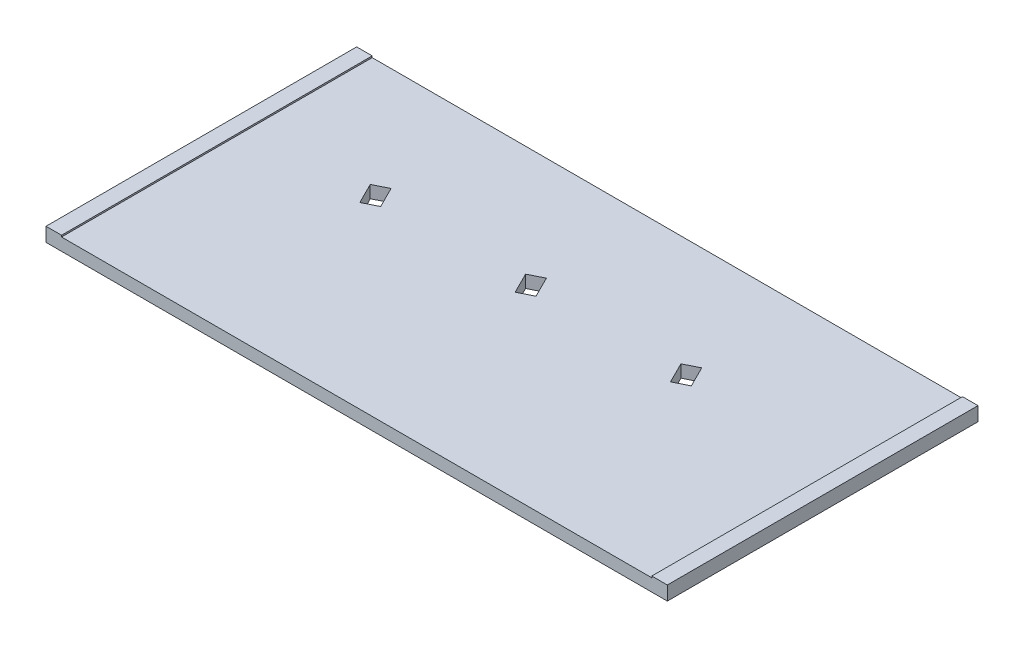
SolidWorks part; units mm, degrees
ref_plane "Front Plane" through (0, 0, 0) normal (0, 0, 1) x (1, 0, 0)
ref_plane "Top Plane" through (0, 0, 0) normal (0, 1, 0) x (1, 0, 0)
ref_plane "Right Plane" through (0, 0, 0) normal (1, 0, 0) x (0, 0, -1)
sketch "Sketch1" plane through (0, 0, 0) normal (0, 1, 0) x (1, 0, 0)
  line L1 (-50.8, -25.4) -> (50.8, -25.4)
  line L2 (-50.8, -25.4) -> (-50.8, 25.4)
  line L3 (-50.8, 25.4) -> (50.8, 25.4)
  line L4 (50.8, -25.4) -> (50.8, 25.4)
  line L5 (0, 25.4) -> (0, -25.4) construction
  line L6 (-50.8, 0) -> (50.8, 0) construction
  point P0 (0, 0)
  dimension "D1" = 50.8
  dimension "D2" = 101.6
extrude "Boss-Extrude1" add sketch "Sketch1" along normal blind 2.032
sketch "Sketch2" plane through (0, 2.032, 0) normal (0, 1, 0) x (1, 0, 0)
  line L0 (-3.3577, 3.8746) -> (-1.0859, 5.0107)
  line L1 (-3.3577, 3.8746) -> (-5.0618, 7.2822)
  line L2 (-1.0859, 5.0107) -> (-2.7901, 8.4183)
  line L3 (-5.0618, 7.2822) -> (-2.7901, 8.4183)
  line L5 (-1.2573, 0) -> (1.2573, 0) construction
  circle A0 centre (0, 0) radius 5.127 construction
  dimension "D1" = 10.254
  dimension "D3" = 3.81
  dimension "D4" = 2.54
  dimension "D2" = 63.43
extrude "Cut-Extrude1" cut sketch "Sketch2" against normal through all contours L3 L1 L0 L2 region at (-3.0739, 2.032, -6.1464)
sketch "Sketch3" plane through (0, 2.032, 0) normal (0, 1, 0) x (1, 0, 0)
  line L0 (-7.112, 8.89) -> (-2.032, 8.89)
  line L1 (-7.112, 8.89) -> (-7.112, 11.43)
  line L2 (-2.032, 8.89) -> (-2.032, 11.43)
  line L3 (-7.112, 11.43) -> (-2.032, 11.43)
  line L4 (-1.2573, 0) -> (1.2573, 0) construction
  line L5 (0, -1.2573) -> (0, 1.2573) construction
  dimension "D1" = 2.54
  dimension "D2" = 5.08
  dimension "D3" = 2.032
  dimension "D4" = 8.89
pattern_linear "LPattern1" count 2 spacing 25.4 along (-1, 0, 0) count 2 spacing 25.4 along (1, 0, 0) of "Cut-Extrude1"
sketch "Sketch4" plane through (0, 2.032, 0) normal (0, 1, 0) x (1, 0, 0)
  line L0 (-50.8, -25.4) -> (50.8, -25.4) construction
  line L1 (-50.8, 25.4) -> (-48.26, 25.4)
  line L2 (-50.8, 25.4) -> (-50.8, -25.4)
  line L3 (-50.8, -25.4) -> (-48.26, -25.4)
  line L4 (-48.26, 25.4) -> (-48.26, -25.4)
  line L6 (50.8, 25.4) -> (48.26, 25.4)
  line L7 (50.8, 25.4) -> (50.8, -25.4)
  line L8 (50.8, -25.4) -> (48.26, -25.4)
  line L9 (48.26, 25.4) -> (48.26, -25.4)
  line M10 (50.8, -25.4) -> (50.8, 25.4)
  line M11 (50.8, 25.4) -> (-50.8, 25.4)
  line M12 (-50.8, 25.4) -> (-50.8, -25.4)
  line M13 (-50.8, -25.4) -> (50.8, -25.4)
  dimension "D1" = 2.54
extrude "Boss-Extrude2" add sketch "Sketch4" along normal blind 0.254 contours L4 M11 M12 M13 | L9 M11 M13 M10 | L2 L1 L4 L3 region at (-49.53, 2.032, 0) region at (49.53, 2.032, 0)
equation "\"Arrow Height\"= 1in"
equation "\"Button Height\"= 2in"
equation "\"Button Width\"= 4in"
equation "\"Haptic Diameter\"= 10mm"
equation "\"Haptic Thickness\"= 2.7mm"
equation "\"D1@Sketch1\"=\"Button Height\""
equation "\"D2@Sketch1\"=\"Button Width\""
equation "\"D1@Sketch2\"=\"Haptic Diameter\"+.01in"
equation "\"Arrow Spacing\"= 1in"
equation "\"Arrow Width\" = 0.75in"
equation "\"Haptic Wire Angle\" = 63.43"
equation "\"Haptic Wire Width\" = .1in"
equation "\"Hatic Wire Height\"= .15in"
equation "\"D2@Sketch2\"=\"Haptic Wire Angle\""
equation "\"D4@Sketch2\"=\"Haptic Wire Width\""
equation "\"D3@Sketch2\"=\"Hatic Wire Height\""
